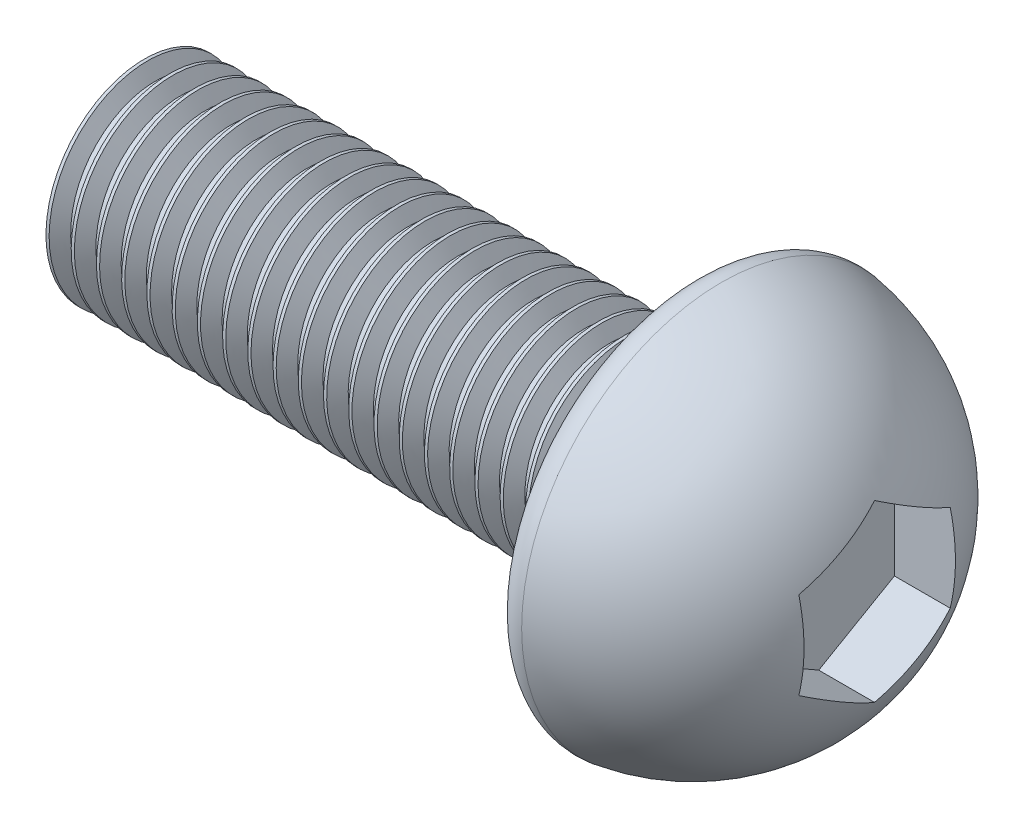
SolidWorks part; units mm, degrees
ref_plane "Front Plane" through (0, 0, 0) normal (0, 0, 1) x (1, 0, 0)
ref_plane "Top Plane" through (0, 0, 0) normal (0, 1, 0) x (1, 0, 0)
ref_plane "Right Plane" through (0, 0, 0) normal (1, 0, 0) x (0, 0, -1)
sketch "Sketch1" plane through (0, 0, 0) normal (0, 0, 1) x (1, 0, 0)
  line L0 (0, 0) -> (22, 0) construction
  line L1 (0, 0) -> (0, 4)
  line L2 (0, 4) -> (22, 4)
  line L3 (22, 4) -> (22, 8)
  line L4 (22, 0) -> (30, 0) construction
  line L5 (0, 0) -> (30, 0)
  arc A0 (22, 8) -> (30, 0) centre (22, 0) cw
  dimension "D3" = 8
  dimension "D1" = 22
  dimension "D2" = 8
revolve "Revolve1" add sketch "Sketch1" angle 360 about L5
thread "Thread1" pitch 1 method cut profile "Thread Profile1" start angle 0, offset 3, length 0, pitch 1, diameter 8
ref_plane "Plane1" through (-3, 0, -4) normal (0, -1, 0) x (0, 0, -1)
sketch "Thread Profile1" plane through (-3, 0, -4) normal (0, -1, 0) x (0, 0, -1)
  line L0 (0, 0) -> (0, 1) construction
  line L11 (0, 0) -> (0, 0.875)
  line L12 (0, 0.875) -> (-0.5413, 0.5625)
  line L13 (-0.5413, 0.5625) -> (-0.5413, 0.3125)
  line L15 (-0.5413, 0.3125) -> (0, 0)
  line L17 (-0.5413, 0.4375) -> (0, 0.4375) construction
  point P2 (0, 0)
  dimension "Pitch" = 1
  dimension "Profile_Angle" = 60
  dimension "Profile_Land" = 0.25
  dimension "Profile_Height" = 0.5413
ref_plane "Plane2" through (27, 0, 0) normal (-1, 0, 0) x (0, 0, 1)
sketch "Sketch5" plane through (27, 0, 0) normal (-1, 0, 0) x (0, 0, 1)
  line L1 (0, 3.4641) -> (-3, 1.7321)
  line L2 (-3, 1.7321) -> (-3, -1.7321)
  line L3 (-3, -1.7321) -> (0, -3.4641)
  line L4 (0, -3.4641) -> (3, -1.7321)
  line L5 (3, -1.7321) -> (3, 1.7321)
  line L6 (3, 1.7321) -> (0, 3.4641)
  circle A0 centre (0, 0) radius 3 construction
  point P1 (0, 0)
  dimension "D1" = 6
extrude "Cut-Extrude1" cut sketch "Sketch5" against normal blind 10
fillet "Fillet1" radius 1 1 edges at (22, -8, 0)
